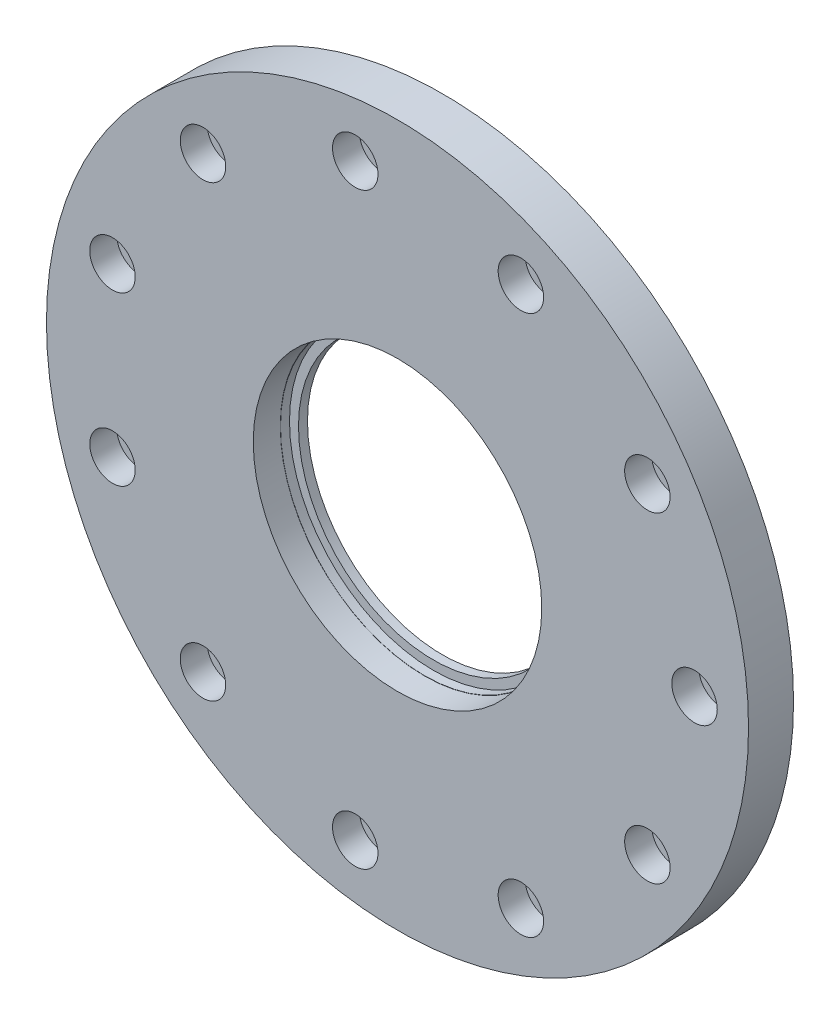
SolidWorks part; units mm, degrees
ref_plane "Front Plane" through (0, 0, 0) normal (0, 0, 1) x (1, 0, 0)
ref_plane "Top Plane" through (0, 0, 0) normal (0, 1, 0) x (1, 0, 0)
ref_plane "Right Plane" through (0, 0, 0) normal (1, 0, 0) x (0, 0, -1)
sketch "Sketch1" plane through (0, 0, 0) normal (0, 0, 1) x (1, 0, 0)
  circle A0 centre (0, 0) radius 39
  circle A1 centre (0, 0) radius 33 construction
  circle A2 centre (33, 0) radius 2.525
  circle A3 centre (27.7614, -17.8411) radius 2.525
  circle A4 centre (13.7087, -30.0179) radius 2.525
  circle A5 centre (-4.6964, -32.6641) radius 2.525
  circle A6 centre (-21.6104, -24.9397) radius 2.525
  circle A7 centre (-31.6633, -9.2972) radius 2.525
  circle A8 centre (-31.6633, 9.2972) radius 2.525
  circle A9 centre (-21.6104, 24.9397) radius 2.525
  circle A10 centre (-4.6964, 32.6641) radius 2.525
  circle A11 centre (13.7087, 30.0179) radius 2.525
  circle A12 centre (27.7614, 17.8411) radius 2.525
  circle A13 centre (0, 0) radius 16.025
  point P28 (0, 0)
extrude "Boss-Extrude1" add sketch "Sketch1" along normal blind 3
sketch "Sketch2" plane through (0, 0, 0) normal (0, 0, -1) x (-1, 0, 0)
  circle A0 centre (0, 0) radius 16
  circle A1 centre (0, 0) radius 39
  dimension "D1" = 32
extrude "Boss-Extrude2" add sketch "Sketch2" along normal blind 2 contours A1 | A0
sketch "Sketch3" plane through (0, 0, 3) normal (0, 0, 1) x (1, 0, 0)
  circle A0 centre (33, 0) radius 1.6
  circle A1 centre (27.7614, -17.8411) radius 1.6
  circle A2 centre (13.7087, -30.0179) radius 1.6
  circle A3 centre (-4.6964, -32.6641) radius 1.6
  circle A4 centre (-21.6104, -24.9397) radius 1.6
  circle A5 centre (-31.6633, -9.2972) radius 1.6
  circle A6 centre (-31.6633, 9.2972) radius 1.6
  circle A7 centre (-21.6104, 24.9397) radius 1.6
  circle A8 centre (-4.6964, 32.6641) radius 1.6
  circle A9 centre (13.7087, 30.0179) radius 1.6
  circle A10 centre (27.7614, 17.8411) radius 1.6
  point P25 (0, 0)
  dimension "D1" = 3.2
  dimension "D2" = 11
extrude "Cut-Extrude1" cut sketch "Sketch3" against normal through all
sketch "Sketch4" plane through (0, 0, -2) normal (0, 0, -1) x (-1, 0, 0)
  circle A0 centre (0, 0) radius 16
  circle A1 centre (0, 0) radius 15
  dimension "D1" = 32
  dimension "D2" = 30
extrude "Boss-Extrude3" add sketch "Sketch4" against normal blind 1
